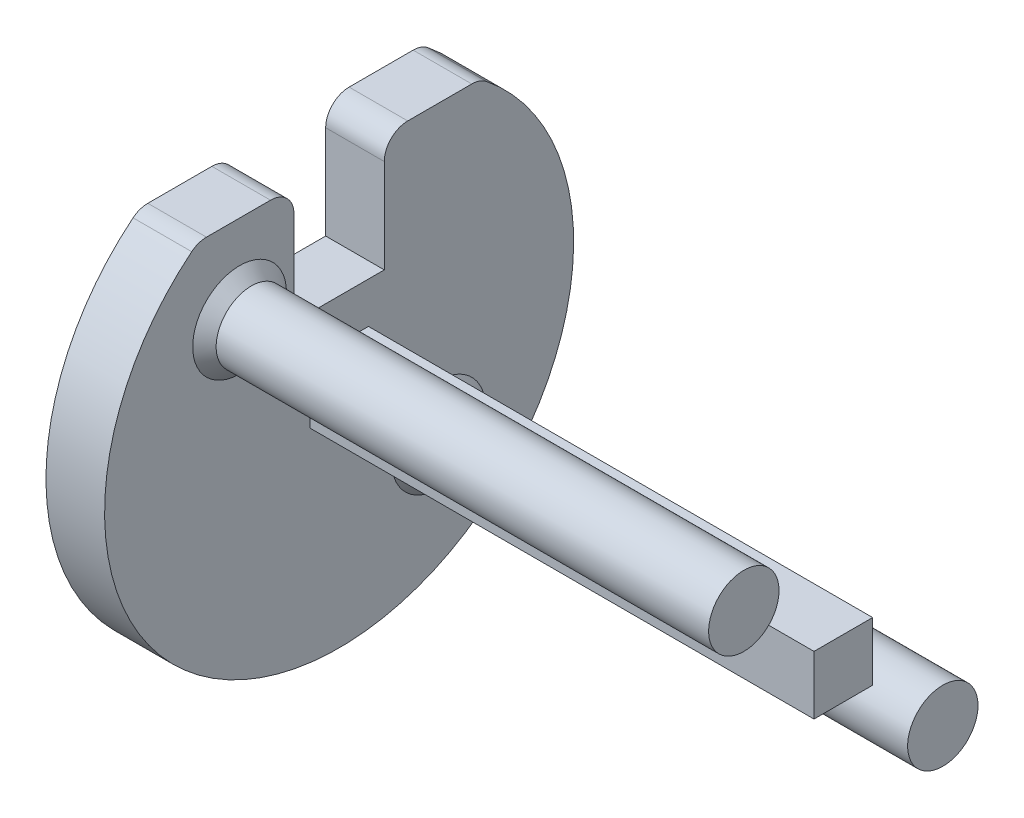
SolidWorks part; units mm, degrees
ref_plane "Front Plane" through (0, 0, 0) normal (0, 0, 1) x (1, 0, 0)
ref_plane "Top Plane" through (0, 0, 0) normal (0, 1, 0) x (1, 0, 0)
ref_plane "Right Plane" through (0, 0, 0) normal (1, 0, 0) x (0, 0, -1)
sketch "Sketch2" plane through (0, 0, 0) normal (1, 0, 0) x (0, 0, -1)
  circle A0 centre (0, 0) radius 20
  dimension "D1" = 40
extrude "Boss-Extrude2" add sketch "Sketch2" along normal blind 5
sketch "Sketch3" plane through (5, 0, 0) normal (1, 0, 0) x (0, 0, -1)
  line L1 (-2.5, -2.5) -> (2.5, -2.5)
  line L2 (-2.5, -2.5) -> (-2.5, 2.5)
  line L3 (-2.5, 2.5) -> (2.5, 2.5)
  line L4 (2.5, -2.5) -> (2.5, 2.5)
  line L5 (-2.5, -2.5) -> (2.5, 2.5) construction
  line L6 (-2.5, 2.5) -> (2.5, -2.5) construction
  point P0 (0, 0)
  dimension "D1" = 5
  dimension "D2" = 5
extrude "Boss-Extrude3" add sketch "Sketch3" along normal blind 43
sketch "Sketch4" plane through (5, 0, 0) normal (1, 0, 0) x (0, 0, -1)
  line L0 (8.4853, -8.4853) -> (-8.4853, 8.4853)
  line L1 (0, 0) -> (0, 50000) construction
  circle A1 centre (-8.4853, 8.4853) radius 3
  circle A2 centre (8.4853, -8.4853) radius 3
  point P4 (0, 0)
  dimension "D3" = 6
  dimension "D4" = 6
  dimension "D1" = 45
  dimension "D2" = 12
extrude "Boss-Extrude4" add sketch "Sketch4" along normal through all contours A1 | A2 region at (5, 9.6009, 11.1785) region at (5, -5.792, -9.6009)
sketch "Sketch5" plane through (5, 0, 0) normal (1, 0, 0) x (0, 0, -1)
  line L0 (2.5, 2.5) -> (-2.5, 2.5) construction
  line L1 (-3.8523, 6) -> (3.8523, 6)
  line L2 (-3.8523, 6) -> (-3.8523, 20)
  line L3 (-3.8523, 20) -> (3.8523, 20)
  line L4 (3.8523, 6) -> (3.8523, 20)
  line L6 (-20, 20) -> (20, 20)
  line L7 (-20, 20) -> (-20, 16)
  line L8 (-20, 16) -> (20, 16)
  line L9 (20, 20) -> (20, 16)
  circle A0 centre (0, 0) radius 20 construction
  point P6 (0, 2.5)
  point P7 (0, 6)
  circle M7 centre (0, 0) radius 20
  dimension "D1" = 14
  dimension "D2" = 4
extrude "Cut-Extrude1" cut sketch "Sketch5" against normal through all contours L8 L2 M7 | L2 L8 L4 M7 | L4 L8 M7 | L8 L2 L1 L4 region at (5, 11, 0) region at (5, 17.3416, 6.8113) region at (5, 17.9394, 0) region at (5, 17.3416, -6.8113)
fillet "Fillet1" radius 2 4 edges at (2.5, 16, -12) (2.5, 16, -3.8523) (2.5, 16, 3.8523) (2.5, 16, 12)
chamfer "Chamfer1" distance 1 angle 45 2 edges at (5, -8.4853, -11.4853) (5, 8.4853, 5.4853)
